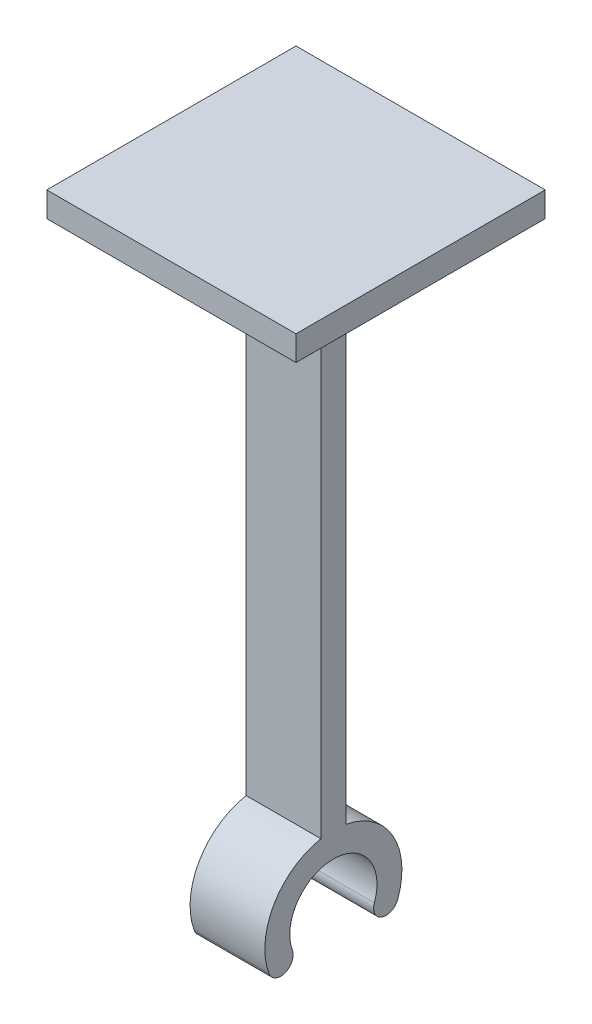
SolidWorks part; units mm, degrees
ref_plane "Front" through (0, 0, 0) normal (0, 0, 1) x (1, 0, 0)
ref_plane "Top" through (0, 0, 0) normal (0, 1, 0) x (1, 0, 0)
ref_plane "Right" through (0, 0, 0) normal (1, 0, 0) x (0, 0, -1)
sketch "Sketch1" plane through (0, 0, 0) normal (1, 0, 0) x (0, 0, -1)
  line L0 (0, 0) -> (-5.5, 0)
  line L1 (0, 0) -> (-5.1683, -1.8811)
  line L2 (0, 50) -> (0, -50) construction
  line L3 (0, 0) -> (5.1683, -1.8811)
  line L4 (-5.1683, -1.8811) -> (-4.2286, -1.5391)
  circle A0 centre (0, 0) radius 3.5
  circle A1 centre (0, 0) radius 5.5
  arc A2 (-5.1683, -1.8811) -> (-3.2889, -1.1971) centre (-4.2286, -1.5391) ccw
  arc A3 (5.1683, -1.8811) -> (3.2889, -1.1971) centre (4.2286, -1.5391) cw
  dimension "D1" = 20
  dimension "D3" = 11
  dimension "D4" = 7
  dimension "D2" = 1
extrude "Boss-Extrude1" add sketch "Sketch1" against normal blind 3 and the other way blind 3 contours L3 A1 L0 A0 | A3 L3 | L0 A1 L1 A0 | L1 A2 region at (0, -0.7903, 4.4817) region at (0, 0.1325, 4.5) region at (0, -1.9379, 4.0835) region at (0, -1.9379, -4.0835)
sketch "Sketch2" plane through (0, 0, 0) normal (1, 0, 0) x (0, 0, -1)
  line L0 (0, 0) -> (0, 5.5)
  line L1 (0, 5.5) -> (0, 3.5)
  line L2 (0, 3.5) -> (-1, 3.5)
  line L4 (-1, 3.5) -> (1, 3.5)
  line L5 (-1, 3.5) -> (-1, 46.5)
  line L6 (-1, 46.5) -> (1, 46.5)
  line L7 (1, 3.5) -> (1, 46.5)
  arc A0 (5.1683, -1.8811) -> (-5.1683, -1.8811) centre (0, 0) ccw construction
  dimension "D1" = 2
  dimension "D2" = 1
  dimension "D3" = 2
  dimension "D4" = 43
extrude "Boss-Extrude2" add sketch "Sketch2" along normal blind 3 contours L4 L7 L6 L5 L2 region at (0, 25, 0)
sketch "Sketch3" plane through (0, 0, 0) normal (1, 0, 0) x (0, 0, -1)
  line L0 (0, 46.5) -> (-1, 46.5)
  line L1 (-1, 46.5) -> (1, 46.5) construction
  line L3 (-1, 46.5) -> (1, 46.5)
  line L4 (-1, 46.5) -> (-1, 3.5)
  line L5 (-1, 3.5) -> (1, 3.5)
  line L6 (1, 46.5) -> (1, 3.5)
  dimension "D1" = 1
  dimension "D2" = 43
  dimension "2" = 2
extrude "Boss-Extrude3" add sketch "Sketch3" against normal blind 3 contours L6 L3 L0 L4 L5 region at (0, 25, 0)
sketch "Sketch4" plane through (0, 46.5, 0) normal (0, 1, 0) x (1, 0, 0)
  line L1 (-10, -10) -> (10, -10)
  line L2 (-10, -10) -> (-10, 10)
  line L3 (-10, 10) -> (10, 10)
  line L4 (10, -10) -> (10, 10)
  line L5 (0, 10) -> (0, -10) construction
  line L6 (-10, 0) -> (10, 0) construction
  point P1 (0, 0)
  dimension "D1" = 20
  dimension "D2" = 20
extrude "Boss-Extrude4" add sketch "Sketch4" along normal blind 2
